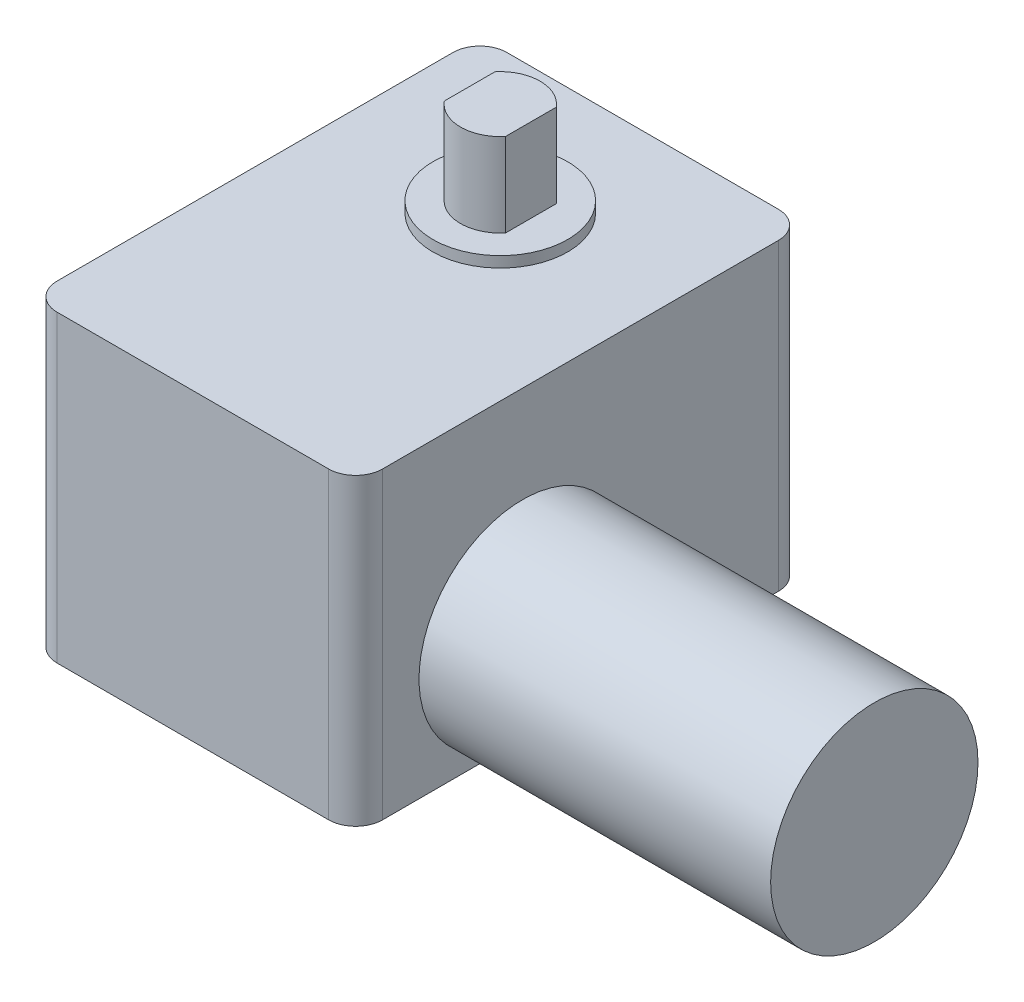
SolidWorks part; units mm, degrees
material "Delrin 2700 NC010, Low Viscosity Acetal Copolymer (SS)"
ref_plane "Front Plane" through (0, 0, 0) normal (0, 0, 1) x (1, 0, 0)
ref_plane "Top Plane" through (0, 0, 0) normal (0, 1, 0) x (1, 0, 0)
ref_plane "Right Plane" through (0, 0, 0) normal (1, 0, 0) x (0, 0, -1)
sketch "Sketch2" plane through (0, 0, 0) normal (0, 1, 0) x (1, 0, 0)
  line L0 (0, 0) -> (0, 16.68)
  line L1 (0, 0) -> (12.07, 0)
  line L2 (0, 16.68) -> (12.07, 16.68)
  line L3 (12.07, 0) -> (12.07, 16.68)
  line L4 (12.07, 2.35) -> (12.07, 10.04)
  line L5 (12.07, 2.35) -> (25.11, 2.35)
  line L7 (25.11, 2.35) -> (25.11, 6.195)
  line L8 (4.8983, 12.34) -> (4.8983, 10.46)
  line L9 (7.1717, 12.34) -> (7.1717, 10.46)
  line L10 (25.11, 6.195) -> (12.07, 6.195)
  circle A0 centre (6.035, 11.4) radius 2.5
  arc A1 (4.8983, 10.46) -> (7.1717, 10.46) centre (6.035, 11.4) ccw
  arc A2 (7.1717, 12.34) -> (4.8983, 12.34) centre (6.035, 11.4) ccw
  point P11 (6.035, 16.68)
  dimension "D7" = 5
  dimension "D8" = 2.95
  dimension "D1" = 12.07
  dimension "D2" = 16.68
  dimension "D3" = 2.35
  dimension "D4" = 3.845
  dimension "D5" = 25.11
  dimension "D6" = 11.4
  dimension "D9" = 1.88
revolve "Revolve1" add sketch "Sketch2" angle 360 about L10 region at (18.59, 0, -4.2725)
extrude "Boss-Extrude1" add sketch "Sketch2<5>" against normal blind 3.845 contours L1 L3 L4 L2 L0 A0 | A0 A2 L9 A1 L8 | L9 A2 L8 A1 region at (6.035, 0, -8.0093) region at (6.035, 0, -11.4) region at (3.6057, 0, -11.4)
sketch "Sketch2<5>" plane through (0, 0, 0) normal (0, 1, 0) x (1, 0, 0) same geometry as "Sketch2"
extrude "Boss-Extrude2" add sketch "Sketch2<6>" along normal blind 7.425 contours L1 L3 L4 L2 L0 A0 region at (6.035, 0, -8.0093)
sketch "Sketch2<6>" plane through (0, 0, 0) normal (0, 1, 0) x (1, 0, 0) same geometry as "Sketch2"
extrude "Boss-Extrude3" add sketch "Sketch2<7>" along normal blind 7.825 contours A0 A2 L9 A1 L8 region at (3.6057, 0, -11.4)
sketch "Sketch2<7>" plane through (0, 0, 0) normal (0, 1, 0) x (1, 0, 0) same geometry as "Sketch2"
extrude "Boss-Extrude4" add sketch "Sketch2<8>" along normal blind 10.925 contours L9 A2 L8 A1 region at (6.035, 0, -11.4)
sketch "Sketch2<8>" plane through (0, 0, 0) normal (0, 1, 0) x (1, 0, 0) same geometry as "Sketch2"
fillet "Fillet1" radius 1 4 edges at (0, 1.79, 0) (12.07, 1.79, 0) (12.07, 1.79, -16.68) (0, 1.79, -16.68)
equation "\"whitemotordepth\"=11.27mm"
equation "\"D1@Boss-Extrude2\"=\"whitemotordepth\" - \"whitemotorbackdepth\""
equation "\"whitemotorbackdepth\"=3.845mm"
equation "\"D1@Boss-Extrude1\"=\"whitemotorbackdepth\""
equation "\"D1@Boss-Extrude3\"=\"whitemotordepth\"-\"whitemotorbackdepth\"+.4"
equation "\"whitemotoraxledepth\" = 3.5mm"
equation "\"D1@Boss-Extrude4\"=\"whitemotoraxledepth\"+\"whitemotordepth\"-\"whitemotorbackdepth\""
equation "\"whitemotoraxleoffset\"=11.4mm"
equation "\"D6@Sketch2\"=\"whitemotoraxleoffset\""
equation "\"whitemotorwidth\"=12.07mm"
equation "\"D1@Sketch2\"=\"whitemotorwidth\""
equation "\"whitemotorheight\"=16.68mm"
equation "\"D2@Sketch2\"=\"whitemotorheight\""
equation "\"whitemotorcylinderlength\" =13.04mm"
equation "\"D5@Sketch2\"=\"whitemotorcylinderlength\"+\"whitemotorwidth\""
equation "\"whitemotorcylinderradius\"=3.845mm"
equation "\"D4@Sketch2\"=\"whitemotorcylinderradius\""
equation "\"whitemotorcylinderoffset\"=2.35mm"
equation "\"D3@Sketch2\"=\"whitemotorcylinderoffset\""
equation "\"whitemotorcutoutlength\"=1.88mm"
equation "\"D9@Sketch2\"=\"whitemotorcutoutlength\""
equation "\"whitemotorouterrad\"=5mm"
equation "\"D7@Sketch2\"=\"whitemotorouterrad\""
equation "\"whitemotorinnerrad\"=2.95mm"
equation "\"D8@Sketch2\"=\"whitemotorinnerrad\""
equation "\"CageLeftBottomEdge\"=22.11mm"
equation "\"CageLeftTopEdge\"=22.11mm"
equation "\"CageRightBottomEdge\"=21.63mm"
equation "\"CageRightTopEdge\"=21.63mm"
equation "\"CageHeight\"=86.04mm"
equation "\"CageLength\"=73.76mm"
equation "\"CageTopScrewClearance\"=10mm"
equation "\"CageBottomScrewClearance\"=25mm"
equation "\"CageLeftTopDepth\"= 11.65mm"
equation "\"CageLeftBottomDepth\"=11.11mm"
equation "\"CageLeftTopHeight\"=8.56175mm"
equation "\"CageLeftBottomHeight\"=16mm"
equation "\"CageRightTopDepth\"= 11.05mm"
equation "\"CageRightBottomDepth\"=10.58mm"
equation "\"CageRightTopHeight\"=9.6mm"
equation "\"CageRightBottomHeight\"=15.49mm"
equation "\"CageLeftTopChannelDepth\"=2.41908mm"
equation "\"CageLeftBottomChannelDepth\"=2.588mm"
equation "\"CageLeftChannelHeight\"=11.7mm"
equation "\"CageRightTopChannelDepth\"=2.32mm"
equation "\"CageRightBottomChannelDepth\"=2.318mm"
equation "\"CageRightChannelHeight\"=10mm"
equation "\"CageChanRelHeight\"=23.99mm"
equation "\"CageChanRelDepth\"=5.492mm"
equation "\"CageChamberRadius\"=16.261mm"
equation "\"CageScrewDiameter\"=4.8mm"
equation "\"CageSetScrewDiameter\"=3.5mm"
equation "\"CageAxleRadius\"=6.639mm"
equation "\"CageAxleKeyHeight\"=1.619mm"
equation "\"CageAxleKeyWidth\"=2.662mm"
equation "\"CageHoseWindowWidth\"=16.29mm"
equation "\"CageHoseWindowHeight\"=26.5mm"
equation "\"CageHoseWindow-Edge\"=8.89mm"
equation "\"CageScrew-VerticalEdge\"=5.0mm"
equation "\"CageScrew-HorizontalEdge\"=7.5mm"
equation "\"CageScrew-HoseCornerScrewEdge\"=4.45mm"
equation "\"CageAxle-BottomEdge\"=56.05mm"
equation "\"CageAxle-FrontEdge\"=46.03mm"
equation "\"CageBackSetScrew-Axle\"=40mm"
equation "\"CageFrontSetScrew-Axle\"=22mm"
equation "\"CageVelocityWindow-BackEdge\"=34.8mm"
equation "\"CageVelocityWindow-BottomEdge\"=27.55mm"
equation "\"CageVelocityWindowHeight\"=22.29mm"
equation "\"CageVelocityWindowWidth\"=12.61mm"
equation "\"TriggerSlot-BottomEdge\"=6.35mm"
equation "\"TriggerSlot-FrontEdge\"=15mm"
equation "\"TriggerSlotSize\"=6.7mm"
equation "\"TriggerRackOffset\"=.236224in"
equation "\"TriggerSlotSizeInt\"=.25in"
equation "\"MotorMountLegLength\"=.25in"
equation "\"GearOffset\"=.264907in"
equation "\"TriggerSlotSpacing\"=.25in"
equation "\"TGMGearFaceDiameter\"=24.40mm"
equation "\"TGMCylinderLength\"=15.00mm"
equation "\"TGMScrewHole-Center\"=8.70mm"
equation "\"TGMScrewHoleDiameter\"=5.04mm"
equation "\"TGMCenterHoleDiameter\"=9.50mm"
equation "\"TGMShaftCollarSideLength\"=19.00mm"
equation "\"TGMShaftCollarDockingDepth\"=7.00mm"
equation "\"TriggerMiniSlotWidth\"=3.5mm"
equation "\"TriggerRackWidth\"=6.5mm"
equation "\"elasticracklength\"=2in"
equation "\"elasticrackpegsize\"=.25in"
equation "\"elasticrackpegbuffer\"=.125in"
equation "\"elasticrackpegspacing\"=1.76476378in"
equation "\"elasticbaybuffer\"=.25in"
equation "\"elasticdepth\"=.125in"
equation "\"elasticbaydepth\"=.75in"
equation "\"motormountwidth\"=12mm"
equation "\"motormountcornerfillet\"=3mm"
